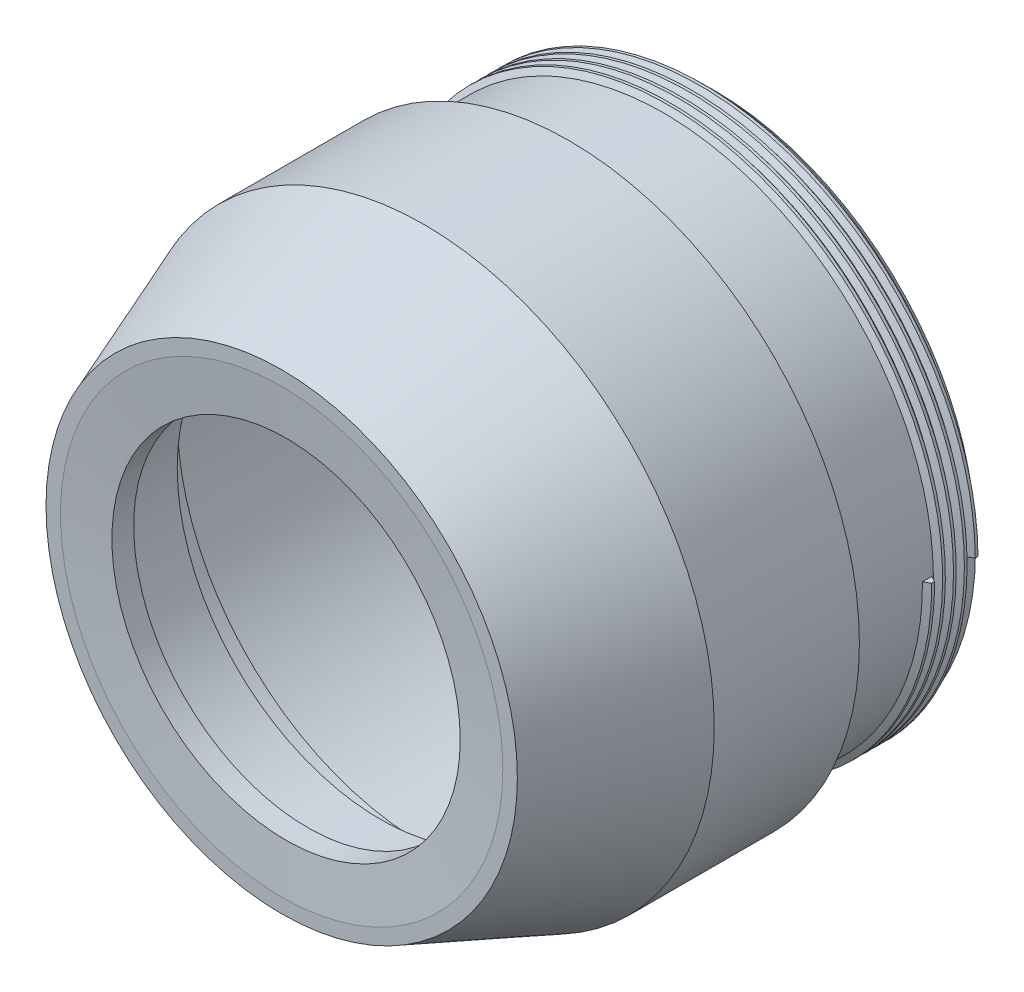
SolidWorks part; units mm, degrees
ref_plane "Ön Düzlem" through (0, 0, 0) normal (0, 0, 1) x (1, 0, 0)
ref_plane "Üst Düzlem" through (0, 0, 0) normal (0, 1, 0) x (1, 0, 0)
ref_plane "Sağ Düzlem" through (0, 0, 0) normal (1, 0, 0) x (0, 0, -1)
sketch "Çizim1" plane through (0, 0, 0) normal (0, 0, 1) x (1, 0, 0)
  circle A0 centre (0, 0) radius 40
  circle A1 centre (0, 0) radius 35
  dimension "D1" = 80
  dimension "D2" = 70
extrude "Yükseklik-Ekstrüzyon1" add sketch "Çizim1" along normal blind 20
ref_plane "Düzlem2" through (0, 0, 20) normal (0, 0, 1) x (1, 0, 0)
sketch "Çizim4" plane through (0, 0, 0) normal (1, 0, 0) x (0, 0, -1)
  line L0 (-20, 34) -> (-20, 40)
  line L1 (-20, 44) -> (-20, -44) construction
  line L4 (-20, 34) -> (-26, 34)
  line L5 (-26, 34) -> (-26, 28)
  line L6 (-26, 28) -> (-36, 28)
  line L7 (-36, 28) -> (-36, 24)
  line L8 (-20, 40) -> (-39.6052, 32.4743)
  line L9 (-36, 24) -> (-39, 24)
  line L10 (-39.6052, 32.4743) -> (-39.6052, 30.4743)
  line L11 (-39.6052, 30.4743) -> (-39, 24)
  dimension "D1" = 6
  dimension "D2" = 21
  dimension "D3" = 4
  dimension "D4" = 10
  dimension "D5" = 6
ref_axis "Eksen1" through (0, 0, 51.387) along (0, 0, -1)
sketch "Çizim14" plane through (-26.9223, 24.1786, 0) normal (0, 0, -1) x (-1, 0, 0)
  circle A1 centre (-26.9223, -24.1786) radius 37
  circle A2 centre (-26.9223, -24.1786) radius 35
extrude "Yükseklik-Ekstrüzyon6" add sketch "Çizim14" along normal blind 20
chamfer "Pah7" distance 1 angle 45 1 edges at (-37, 0, -20)
chamfer "Pah8" distance 1 angle 45 1 edges at (37, 0, 0)
thread "Diş1" pitch 1.5 method extrude profile "Diş Profili1" start angle 0, offset 0, length 6, pitch 1.5, diameter 74
ref_plane "Düzlem3" through (37, 0, -19) normal (0, 1, 0) x (-1, 0, 0)
sketch "Diş Profili1" plane through (37, 0, -19) normal (0, 1, 0) x (-1, 0, 0)
  line L0 (0, 0) -> (0, 1.5) construction
  line L11 (0, 0) -> (0, 1.3125)
  line L12 (0, 1.3125) -> (-0.8119, 0.8437)
  line L13 (-0.8119, 0.8437) -> (-0.8119, 0.4687)
  line L15 (-0.8119, 0.4687) -> (0, 0)
  line L17 (-0.8119, 0.6562) -> (0, 0.6562) construction
  point P2 (0, 0)
  dimension "Pitch" = 1.5
  dimension "Profile_Angle" = 60
  dimension "Profile_Land" = 0.375
  dimension "Profile_Height" = 0.8119
revolve "Döndür2" add sketch "Çizim4" angle 360 about axis through (0, 0, 51.387) along (0, 0, -1)
